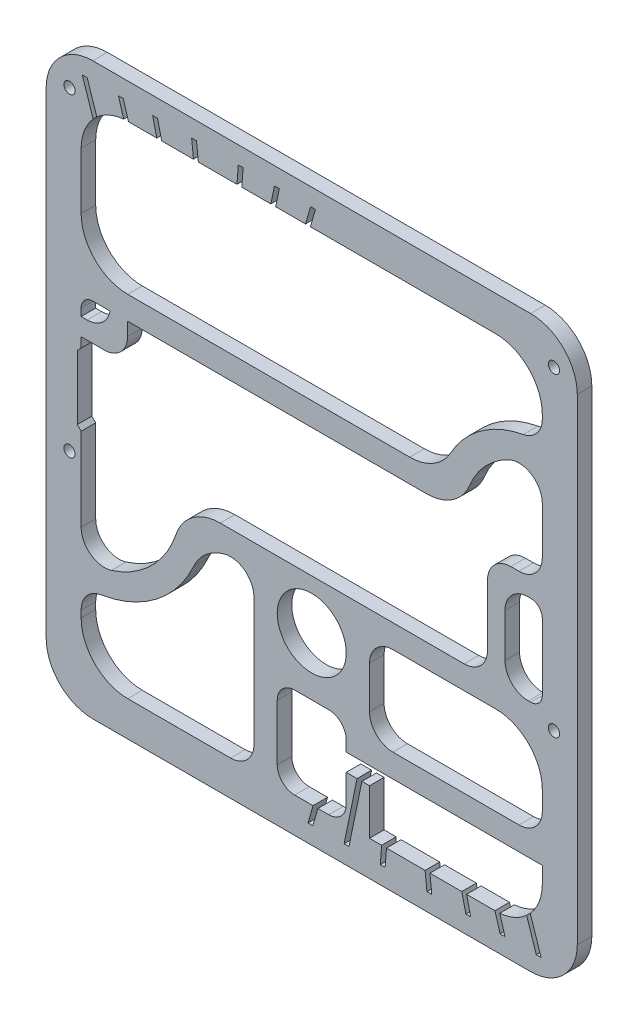
SolidWorks part; units mm, degrees
ref_plane "Front Plane" through (0, 0, 0) normal (0, 0, 1) x (1, 0, 0)
ref_plane "Top Plane" through (0, 0, 0) normal (0, 1, 0) x (1, 0, 0)
ref_plane "Right Plane" through (0, 0, 0) normal (1, 0, 0) x (0, 0, -1)
sketch "Sketch1" plane through (0, 0, 0) normal (0, 0, 1) x (1, 0, 0)
  line L0 (44.642, 23.7892) -> (44.642, 19.9792) construction
  line L1 (-8.1388, 23.7892) -> (49.7286, 23.7892)
  line L2 (-8.1388, 23.7892) -> (-8.1388, -38.311)
  line L3 (-8.1388, -38.311) -> (49.7286, -38.311)
  line L4 (49.7286, 23.7892) -> (49.7286, -38.311)
  line L5 (45.9186, -34.501) -> (-4.3288, -34.501)
  line L6 (45.9186, -34.501) -> (45.9186, 19.9792)
  line L7 (45.9186, 19.9792) -> (-4.3288, 19.9792)
  line L8 (-4.3288, -34.501) -> (-4.3288, 19.9792)
  line L9 (44.642, 21.8842) -> (-35.1587, 21.8842) construction
  line L10 (-4.3288, -31.0517) -> (-8.1388, -31.0517) construction
  line L11 (-6.2338, -31.0517) -> (-6.2338, 6.9585) construction
  line L12 (20.6696, 21.8842) -> (21.1982, 21.8842) construction
  line L13 (-6.2338, -12.887) -> (-6.2338, -25.1298) construction
  line L14 (3.0779, -34.501) -> (3.0779, -38.311) construction
  line L15 (3.0779, -36.406) -> (37.3423, -36.406) construction
  line L17 (49.7286, 15.2205) -> (45.9186, 15.2205) construction
  line L18 (47.8236, 15.2205) -> (47.8236, -0.9437) construction
  line L19 (47.8236, -1.6348) -> (47.8236, 10.608) construction
  line L20 (20.9203, -36.406) -> (20.3916, -36.406) construction
  dimension "D1" = 3.81
  dimension "D2" = 3.81
extrude "Boss-Extrude1" add sketch "Sketch1" along normal blind 1.5875
sketch "Sketch2" plane through (0, 0, 0) normal (0, 0, -1) x (-1, 0, 0)
  line L0 (-45.9186, -34.501) -> (-45.9186, 19.9792) construction
  line L1 (-34.8696, 3.653) -> (4.3288, 3.653)
  line L2 (-45.9186, 3.653) -> (-45.9186, 0.7339)
  line L3 (-37.4096, 1.113) -> (4.3288, 1.113)
  line L4 (4.3288, 3.653) -> (4.3288, 1.113)
  line L5 (4.3288, 19.9792) -> (4.3288, -34.501) construction
  line L6 (-33.4496, 1.113) -> (-36.4496, 1.113) construction
  line L7 (1.2504, -12.887) -> (-36.4496, -12.887) construction
  line L8 (-45.9186, -15.427) -> (-8.8785, -15.427)
  line L9 (-45.9186, -15.427) -> (-45.9186, -12.887)
  line L10 (-45.9186, -12.887) -> (-6.5805, -12.887)
  line L11 (1.357, -21.2563) -> (14.2432, -21.2563) construction
  line L12 (4.3288, -23.7963) -> (4.3288, -26.3363)
  line L13 (-45.9186, 12.162) -> (-45.9186, 9.622)
  arc A0 (-45.9186, 9.622) -> (-37.4096, 1.113) centre (-45.9186, 1.113) cw
  arc A1 (-45.9186, 12.162) -> (-34.8696, 3.653) centre (-45.9186, 0.7339) cw
  arc A2 (4.3288, -23.7963) -> (-6.5805, -12.887) centre (4.3288, -12.887) cw
  arc A3 (-8.8785, -15.427) -> (4.3288, -26.3363) centre (4.3288, -12.887) ccw
  circle A5 centre (1.357, -18.2591) radius 2.9972 construction
  line M5 (-45.9186, -34.501) -> (-45.9186, 19.9792)
  line M7 (4.3288, 19.9792) -> (4.3288, -34.501)
  dimension "D5" = 2.54
  dimension "D1" = 2.54
  dimension "D2" = 2.54
  dimension "D3" = 2.54
  dimension "D4" = 2.54
  dimension "D6" = 2.54
  dimension "D7" = 2.54
extrude "Boss-Extrude2" add sketch "Sketch2" against normal up to surface (1.5875 mm away) contours A1 A0 L3 L1 M5 M7 | L10 L8 M5 M7 region at (15.2704, 3.1385, 0) region at (-3.8086, -25.0663, 0) up to face at (20.7949, -7.2609, 1.5875)
sketch "Sketch3" plane through (0, 0, 0) normal (0, 0, -1) x (-1, 0, 0)
  line L0 (-45.9186, -1.1649) -> (-39.9496, -1.1649)
  line L1 (-45.9186, -12.887) -> (-45.9186, 9.622) construction
  line L2 (-39.9496, -4.387) -> (-39.9496, -11.387) construction
  line L3 (-39.9496, -1.1649) -> (-39.9496, -12.887)
  line L4 (-45.9186, -12.887) -> (-6.5805, -12.887) construction
  line L5 (-39.9496, -12.887) -> (-41.8546, -12.887)
  line L6 (-41.8546, -12.887) -> (-41.8546, -3.0699)
  line L7 (-41.8546, -3.0699) -> (-45.9186, -3.0699)
  line L8 (-45.9186, -3.0699) -> (-45.9186, -1.1649)
  line L9 (-42.9468, 0.7401) -> (-53.4831, 0.7401) construction
  line L10 (-0.7296, 1.113) -> (-0.7296, -2.887)
  line L11 (-37.4096, 1.113) -> (4.3288, 1.113) construction
  line L12 (-1.9996, -2.887) -> (1.2504, -2.887) construction
  line L13 (-0.7296, -2.887) -> (4.3288, -2.887)
  line L14 (4.3288, 1.113) -> (4.3288, -23.7963) construction
  line L15 (4.3288, -2.887) -> (4.3288, -0.982)
  line L16 (4.3288, -0.982) -> (1.1754, -0.982)
  line L17 (1.1754, -0.982) -> (1.1754, 1.113)
  line L18 (1.1754, 1.113) -> (-0.7296, 1.113)
  circle A0 centre (-42.9468, 3.7373) radius 2.9972 construction
  dimension "D1" = 1.905
  dimension "D2" = 1.905
  dimension "D3" = 1.905
  dimension "D4" = 1.905
  dimension "D5" = 1.27
  dimension "D6" = 1.905
extrude "Boss-Extrude3" add sketch "Sketch3" against normal up to surface (1.5875 mm away) up to face at (21.2778, -6.3699, 1.5875)
fillet "Fillet1" radius 5.08 4 edges at (49.7286, -38.311, 0.7937) (-8.1388, -38.311, 0.7937) (-8.1388, 23.7892, 0.7937) (49.7286, 23.7892, 0.7937)
fillet "Fillet2" radius 5.08 10 edges at (8.8785, -15.427, 0.7937) (45.9186, -15.427, 0.7937) (45.9186, -34.501, 0.7937) (-4.3288, -34.501, 0.7937) (34.8696, 3.653, 0.7937) (-4.3288, 3.653, 0.7937) (45.9186, 19.9792, 0.7937) (-4.3288, 19.9792, 0.7937) (6.5805, -12.887, 0.7937) (37.4096, 1.113, 0.7937)
fillet "Fillet3" radius 2.54 11 edges at (41.8546, -3.0699, 0.7938) (39.9496, -12.887, 0.7938) (41.8546, -12.887, 0.7938) (39.9496, -1.1649, 0.7938) (45.9186, -1.1649, 0.7938) (-1.1754, -0.982, 0.7938) (0.7296, -2.887, 0.7938) (45.9186, 9.622, 0.7937) (-4.3288, -26.3363, 0.7937) (-4.3288, -23.7963, 0.7937) (45.9186, 12.162, 0.7937)
fillet "Fillet4" radius 1.27 3 edges at (45.9186, -12.887, 0.7937) (45.9186, -3.0699, 0.7938) (-4.3288, 1.113, 0.7937)
sketch "Sketch5" plane through (0, 0, 0) normal (0, 0, -1) x (-1, 0, 0)
  line L0 (-40.8386, -15.427) -> (-12.5612, -15.427) construction
  line L1 (-27.0941, -15.427) -> (-14.4957, -15.427)
  line L2 (-27.0941, -15.427) -> (-27.0941, -34.501)
  line L3 (-27.0941, -34.501) -> (-14.4957, -34.501)
  line L4 (-14.4957, -15.427) -> (-14.4957, -34.501)
  line L5 (-0.7512, -34.501) -> (-40.8386, -34.501) construction
  line L6 (-24.5541, -18.2972) -> (-27.0941, -18.2972) construction
  line L9 (-17.0357, -18.2972) -> (-14.4957, -18.2972) construction
  circle A1 centre (-20.7949, -18.2972) radius 3.7592 construction
  dimension "D1" = 2.54
extrude "Boss-Extrude4" add sketch "Sketch5" against normal up to surface (1.5875 mm away) up to face at (-3.29, -0.0173, 1.5875)
sketch "Sketch6" plane through (0, 0, 0) normal (0, 0, -1) x (-1, 0, 0)
  circle A0 centre (-20.7949, -18.2972) radius 3.7592 construction
  circle A1 centre (-20.7949, -18.2972) radius 3.7592
extrude "Cut-Extrude2" cut sketch "Sketch6" against normal up to surface (1.5875 mm away) up to face at (4.8008, -25.4732, 1.5875)
sketch "Sketch7" plane through (0, 0, 0) normal (0, 0, -1) x (-1, 0, 0)
  line L0 (-27.0941, -15.427) -> (-27.0941, -34.501) construction
  line L1 (-24.5541, -24.5964) -> (-17.0357, -24.5964)
  line L2 (-24.5541, -24.5964) -> (-24.5541, -34.501)
  line L3 (-24.5541, -34.501) -> (-17.0357, -34.501)
  line L4 (-17.0357, -24.5964) -> (-17.0357, -34.501)
  line L5 (-14.4957, -34.501) -> (-14.4957, -15.427) construction
  line L6 (-0.7512, -34.501) -> (-14.4957, -34.501) construction
  line L7 (-20.7949, -22.0564) -> (-6.5424, -22.0564) construction
  line L8 (-20.7949, -22.0564) -> (-20.7949, -21.3452) construction
  circle A0 centre (-20.7949, -18.2972) radius 3.7592 construction
  dimension "D1" = 2.54
  dimension "D2" = 2.54
  dimension "D3" = 2.54
extrude "Cut-Extrude3" cut sketch "Sketch7" against normal up to surface (1.5875 mm away) up to face at (24.5541, -18.2972, 1.5875)
fillet "Fillet5" radius 1.905 4 edges at (24.5541, -34.501, 0.7937) (17.0357, -34.501, 0.7938) (17.0357, -24.5964, 0.7938) (24.5541, -24.5964, 0.7938)
sketch "Sketch8" plane through (0, 0, 0) normal (0, 0, -1) x (-1, 0, 0)
  line L0 (-45.9186, -29.421) -> (-45.9186, -20.507) construction
  line L1 (-45.9186, -25.103) -> (-27.0941, -25.103)
  line L2 (-45.9186, -25.103) -> (-45.9186, -27.643)
  line L3 (-45.9186, -27.643) -> (-27.0941, -27.643)
  line L4 (-27.0941, -25.103) -> (-27.0941, -27.643)
  line L5 (-27.0941, -15.427) -> (-27.0941, -34.501) construction
  line L6 (-45.7916, -27.643) -> (-20.3916, -27.643) construction
  dimension "D1" = 2.54
extrude "Boss-Extrude5" add sketch "Sketch8" against normal up to surface (1.5875 mm away) up to face at (20.7949, -29.5487, 1.5875)
fillet "Fillet6" radius 2.54 5 edges at (27.0941, -15.427, 0.7937) (14.4957, -15.427, 0.7937) (14.4957, -34.501, 0.7937) (27.0941, -25.103, 0.7937) (45.9186, -25.103, 0.7937)
sketch "Sketch4" plane through (0, 0, 0) normal (0, 0, -1) x (-1, 0, 0)
  line L0 (3.2504, -2.887) -> (4.7504, -4.387) construction
  line L1 (4.7504, -11.387) -> (3.2504, -12.887) construction
  line L2 (3.2504, -2.887) -> (4.7504, -4.387)
  line L3 (4.7504, -11.387) -> (3.2504, -12.887)
  line L4 (4.7504, -4.387) -> (4.7504, -11.387) construction
  line L5 (4.7504, -4.387) -> (4.7504, -11.387)
  line L6 (3.2504, -2.887) -> (3.2504, -12.887)
  line L32 (4.2018, 13.1212) -> (4.2018, 15.0262)
  line L33 (4.2018, 15.0262) -> (1.9364, 15.0262)
  line L34 (1.9364, 15.0262) -> (4.2018, 21.8842)
  line L35 (4.2018, 21.8842) -> (3.6731, 21.8842)
  line L36 (3.6731, 21.8842) -> (1.4078, 15.0262)
  line L37 (1.4078, 15.0262) -> (-1.7768, 15.0262)
  line L38 (-1.7768, 15.0262) -> (0.2648, 21.8842)
  line L39 (0.2648, 21.8842) -> (-0.2639, 21.8842)
  line L40 (-0.2639, 21.8842) -> (-2.3054, 15.0262)
  line L41 (-2.3054, 15.0262) -> (-5.0788, 15.0262)
  line L42 (-5.0788, 15.0262) -> (-3.469, 21.8842)
  line L43 (-3.469, 21.8842) -> (-3.9977, 21.8842)
  line L44 (-3.9977, 21.8842) -> (-5.6074, 15.0262)
  line L45 (-5.6074, 15.0262) -> (-8.4316, 15.0262)
  line L46 (-8.4316, 15.0262) -> (-7.7108, 21.8842)
  line L47 (-7.7108, 21.8842) -> (-8.2395, 21.8842)
  line L48 (-8.2395, 21.8842) -> (-8.9602, 15.0262)
  line L49 (-8.9602, 15.0262) -> (-12.267, 15.0262)
  line L50 (-12.267, 15.0262) -> (-12.7956, 21.8842)
  line L51 (-12.7956, 21.8842) -> (-13.3242, 21.8842)
  line L52 (-13.3242, 21.8842) -> (-12.7956, 15.0262)
  line L53 (-12.7956, 15.0262) -> (-15.3277, 15.0262)
  line L54 (-15.3277, 15.0262) -> (-16.7326, 21.8842)
  line L55 (-16.7326, 21.8842) -> (-17.2612, 21.8842)
  line L56 (-17.2612, 21.8842) -> (-15.8563, 15.0262)
  line L57 (-15.8563, 15.0262) -> (-18.6963, 15.0262)
  line L58 (-18.6963, 15.0262) -> (-20.6696, 21.8842)
  line L59 (-20.6696, 21.8842) -> (-21.1982, 21.8842)
  line L60 (-21.1982, 21.8842) -> (-19.225, 15.0262)
  line L61 (-19.225, 15.0262) -> (-21.1982, 15.0262)
  line L62 (-21.1982, 15.0262) -> (-21.1982, 13.1212)
  line L63 (-21.1982, 13.1212) -> (4.2018, 13.1212)
  line L64 (4.2018, 13.1212) -> (4.2018, 15.0262)
  line L65 (4.2018, 15.0262) -> (1.9364, 15.0262)
  line L66 (1.9364, 15.0262) -> (4.2018, 21.8842)
  line L67 (4.2018, 21.8842) -> (3.6731, 21.8842)
  line L68 (3.6731, 21.8842) -> (1.4078, 15.0262)
  line L69 (1.4078, 15.0262) -> (-1.7768, 15.0262)
  line L70 (-1.7768, 15.0262) -> (0.2648, 21.8842)
  line L71 (0.2648, 21.8842) -> (-0.2639, 21.8842)
  line L72 (-0.2639, 21.8842) -> (-2.3054, 15.0262)
  line L73 (-2.3054, 15.0262) -> (-5.0788, 15.0262)
  line L74 (-5.0788, 15.0262) -> (-3.469, 21.8842)
  line L75 (-3.469, 21.8842) -> (-3.9977, 21.8842)
  line L76 (-3.9977, 21.8842) -> (-5.6074, 15.0262)
  line L77 (-5.6074, 15.0262) -> (-8.4316, 15.0262)
  line L78 (-8.4316, 15.0262) -> (-7.7108, 21.8842)
  line L79 (-7.7108, 21.8842) -> (-8.2395, 21.8842)
  line L80 (-8.2395, 21.8842) -> (-8.9602, 15.0262)
  line L81 (-8.9602, 15.0262) -> (-12.267, 15.0262)
  line L82 (-12.267, 15.0262) -> (-12.7956, 21.8842)
  line L83 (-12.7956, 21.8842) -> (-13.3242, 21.8842)
  line L84 (-13.3242, 21.8842) -> (-12.7956, 15.0262)
  line L85 (-12.7956, 15.0262) -> (-15.3277, 15.0262)
  line L86 (-15.3277, 15.0262) -> (-16.7326, 21.8842)
  line L87 (-16.7326, 21.8842) -> (-17.2612, 21.8842)
  line L88 (-17.2612, 21.8842) -> (-15.8563, 15.0262)
  line L89 (-15.8563, 15.0262) -> (-18.6963, 15.0262)
  line L90 (-18.6963, 15.0262) -> (-20.6696, 21.8842)
  line L91 (-20.6696, 21.8842) -> (-21.1982, 21.8842)
  line L92 (-21.1982, 21.8842) -> (-19.225, 15.0262)
  line L93 (-19.225, 15.0262) -> (-21.1982, 15.0262)
  line L94 (-21.1982, 15.0262) -> (-21.1982, 13.1212)
  line L95 (-21.1982, 13.1212) -> (4.2018, 13.1212)
  line L96 (-45.7916, -27.643) -> (-45.7916, -29.548)
  line L97 (-45.7916, -29.548) -> (-43.5263, -29.548)
  line L98 (-43.5263, -29.548) -> (-45.7916, -36.406)
  line L99 (-45.7916, -36.406) -> (-45.263, -36.406)
  line L100 (-45.263, -36.406) -> (-42.9976, -29.548)
  line L101 (-42.9976, -29.548) -> (-39.8131, -29.548)
  line L102 (-39.8131, -29.548) -> (-41.8546, -36.406)
  line L103 (-41.8546, -36.406) -> (-41.326, -36.406)
  line L104 (-41.326, -36.406) -> (-39.2845, -29.548)
  line L105 (-39.2845, -29.548) -> (-36.5111, -29.548)
  line L106 (-36.5111, -29.548) -> (-38.1208, -36.406)
  line L107 (-38.1208, -36.406) -> (-37.5922, -36.406)
  line L108 (-37.5922, -36.406) -> (-35.9825, -29.548)
  line L109 (-35.9825, -29.548) -> (-33.1583, -29.548)
  line L110 (-33.1583, -29.548) -> (-33.879, -36.406)
  line L111 (-33.879, -36.406) -> (-33.3504, -36.406)
  line L112 (-33.3504, -36.406) -> (-32.6297, -29.548)
  line L113 (-32.6297, -29.548) -> (-29.3229, -29.548)
  line L114 (-29.3229, -29.548) -> (-28.7943, -36.406)
  line L115 (-28.7943, -36.406) -> (-28.2656, -36.406)
  line L116 (-28.2656, -36.406) -> (-28.7943, -29.548)
  line L117 (-28.7943, -29.548) -> (-26.2622, -29.548)
  line L118 (-26.2622, -29.548) -> (-24.8573, -36.406)
  line L119 (-24.8573, -36.406) -> (-24.3286, -36.406)
  line L120 (-24.3286, -36.406) -> (-25.7336, -29.548)
  line L121 (-25.7336, -29.548) -> (-22.8935, -29.548)
  line L122 (-22.8935, -29.548) -> (-20.9203, -36.406)
  line L123 (-20.9203, -36.406) -> (-20.3916, -36.406)
  line L124 (-20.3916, -36.406) -> (-22.3649, -29.548)
  line L125 (-22.3649, -29.548) -> (-20.3916, -29.548)
  line L126 (-20.3916, -29.548) -> (-20.3916, -27.643)
  line L127 (-20.3916, -27.643) -> (-45.7916, -27.643)
  line L128 (-45.7916, -27.643) -> (-45.7916, -29.548)
  line L129 (-45.7916, -29.548) -> (-43.5263, -29.548)
  line L130 (-43.5263, -29.548) -> (-45.7916, -36.406)
  line L131 (-45.7916, -36.406) -> (-45.263, -36.406)
  line L132 (-45.263, -36.406) -> (-42.9976, -29.548)
  line L133 (-42.9976, -29.548) -> (-39.8131, -29.548)
  line L134 (-39.8131, -29.548) -> (-41.8546, -36.406)
  line L135 (-41.8546, -36.406) -> (-41.326, -36.406)
  line L136 (-41.326, -36.406) -> (-39.2845, -29.548)
  line L137 (-39.2845, -29.548) -> (-36.5111, -29.548)
  line L138 (-36.5111, -29.548) -> (-38.1208, -36.406)
  line L139 (-38.1208, -36.406) -> (-37.5922, -36.406)
  line L140 (-37.5922, -36.406) -> (-35.9825, -29.548)
  line L141 (-35.9825, -29.548) -> (-33.1583, -29.548)
  line L142 (-33.1583, -29.548) -> (-33.879, -36.406)
  line L143 (-33.879, -36.406) -> (-33.3504, -36.406)
  line L144 (-33.3504, -36.406) -> (-32.6297, -29.548)
  line L145 (-32.6297, -29.548) -> (-29.3229, -29.548)
  line L146 (-29.3229, -29.548) -> (-28.7943, -36.406)
  line L147 (-28.7943, -36.406) -> (-28.2656, -36.406)
  line L148 (-28.2656, -36.406) -> (-28.7943, -29.548)
  line L149 (-28.7943, -29.548) -> (-26.2622, -29.548)
  line L150 (-26.2622, -29.548) -> (-24.8573, -36.406)
  line L151 (-24.8573, -36.406) -> (-24.3286, -36.406)
  line L152 (-24.3286, -36.406) -> (-25.7336, -29.548)
  line L153 (-25.7336, -29.548) -> (-22.8935, -29.548)
  line L154 (-22.8935, -29.548) -> (-20.9203, -36.406)
  line L155 (-20.9203, -36.406) -> (-20.3916, -36.406)
  line L156 (-20.3916, -36.406) -> (-22.3649, -29.548)
  line L157 (-22.3649, -29.548) -> (-20.3916, -29.548)
  line L158 (-20.3916, -29.548) -> (-20.3916, -27.643)
  line L159 (-20.3916, -27.643) -> (-45.7916, -27.643)
  dimension "D1" = 0
  dimension "D2" = 0
extrude "Cut-Extrude1" cut sketch "Sketch4" against normal up to surface (1.5875 mm away) up to face at (37.5833, -30.9522, 1.5875)
sketch "Sketch9" plane through (0, 0, 0) normal (0, 0, -1) x (-1, 0, 0)
  circle A0 centre (-47.1886, 19.9792) radius 0.6096 construction
  circle A1 centre (5.5988, 19.9792) radius 0.6096 construction
  circle A2 centre (5.5988, -14.308) radius 0.6096 construction
  circle A3 centre (-47.1886, -14.308) radius 0.6096 construction
  circle A4 centre (-47.1886, 19.9792) radius 0.6096
  circle A5 centre (5.5988, 19.9792) radius 0.6096
  circle A6 centre (5.5988, -14.308) radius 0.6096
  circle A7 centre (-47.1886, -14.308) radius 0.6096
extrude "Cut-Extrude4" cut sketch "Sketch9" against normal up to surface (1.5875 mm away) up to face at (18.1234, -5.3808, 1.5875)
